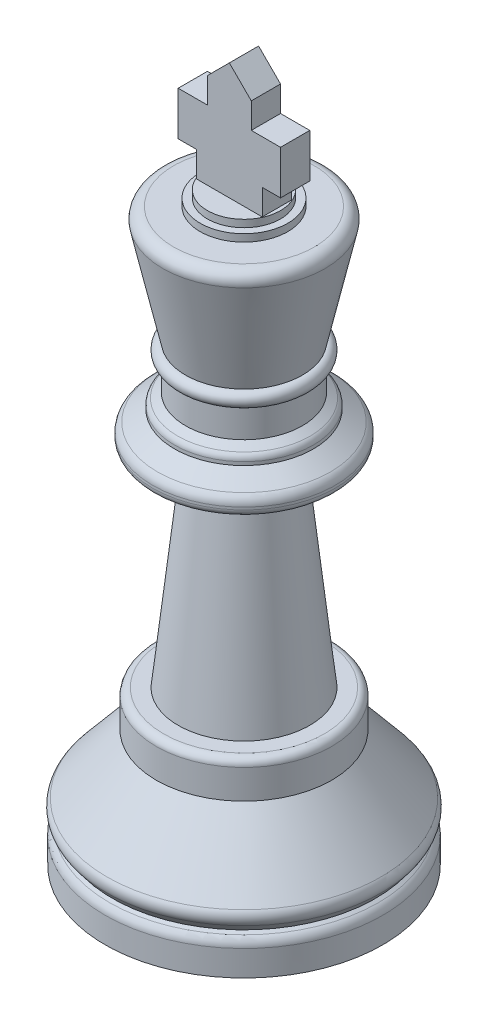
SolidWorks part; units mm, degrees
ref_plane "Front Plane" through (0, 0, 0) normal (0, 0, 1) x (1, 0, 0)
ref_plane "Top Plane" through (0, 0, 0) normal (0, 1, 0) x (1, 0, 0)
ref_plane "Right Plane" through (0, 0, 0) normal (1, 0, 0) x (0, 0, -1)
sketch "Sketch1" plane through (0, 0, 0) normal (0, 0, 1) x (1, 0, 0)
  line L0 (0, 0) -> (0, 80)
  line L1 (0, 80) -> (5, 80)
  line L2 (5, 80) -> (5, 79)
  line L3 (5, 79) -> (6, 79)
  line L4 (6, 79) -> (6, 78)
  line L5 (6, 78) -> (11.5, 78)
  line L6 (11.5, 78) -> (8, 62)
  line L8 (8, 60) -> (8, 56)
  line L9 (8, 56) -> (9.5, 55)
  line L10 (9.5, 55) -> (9.5, 54)
  line L11 (9.5, 54) -> (12.5, 52)
  line L12 (12.5, 52) -> (12.5, 50)
  line L13 (12.5, 50) -> (6, 49)
  line L14 (6, 49) -> (9, 21)
  line L15 (9, 21) -> (12, 21)
  line L16 (12, 21) -> (12, 16)
  line L17 (12, 16) -> (19.5, 7)
  line L18 (19.5, 7) -> (18, 5)
  line L19 (18, 5) -> (19, 4.25)
  line L20 (19, 4.25) -> (19, 0)
  line L21 (19, 0) -> (0, 0)
  arc A0 (8, 60) -> (8, 62) centre (8, 61) ccw
  dimension "D8" = 1
  dimension "D1" = 80
  dimension "D2" = 5
  dimension "D3" = 1
  dimension "D4" = 1
  dimension "D6" = 11.5
  dimension "D7" = 62
  dimension "D9" = 8
  dimension "D11" = 56
  dimension "D12" = 55
  dimension "D13" = 9.5
  dimension "D10" = 8
  dimension "D14" = 12.5
  dimension "D15" = 1
  dimension "D16" = 50
  dimension "D17" = 49
  dimension "D18" = 6
  dimension "D19" = 21
  dimension "D20" = 9
  dimension "D21" = 12
  dimension "D22" = 5
  dimension "D23" = 5
  dimension "18" = 18
  dimension "D25" = 19
  dimension "D26" = 7
  dimension "D24" = 19.5
revolve "Revolve1" add sketch "Sketch1" angle 360 about L0
sketch "Sketch2" plane through (0, 0, 0) normal (0, 0, 1) x (1, 0, 0)
  line L0 (0, 80) -> (0, 96)
  line L1 (5, 80) -> (-5, 80) construction
  line L2 (0, 96) -> (3, 93)
  line L3 (3, 93) -> (3, 89.5)
  line L4 (3, 89.5) -> (7, 89.5)
  line L5 (7, 89.5) -> (7, 83.5)
  line L6 (7, 83.5) -> (4.5, 83.5)
  line L7 (4.5, 83.5) -> (4.5, 80)
  line L8 (4.5, 80) -> (0, 80)
  dimension "D1" = 3.5
  dimension "D2" = 2.5
  dimension "D3" = 4.5
  dimension "D4" = 3
  dimension "D5" = 6
  dimension "D6" = 16
  dimension "D7" = 3.5
extrude "Boss-Extrude1" add sketch "Sketch2" along normal blind 2 and the other way blind 2
mirror "Mirror1" about plane through (0, 80, -2) normal (-1, 0, 0) of "Boss-Extrude1"
fillet "Fillet1" radius 1.5 4 edges at (0, 4.25, -19) (0, 7, -19.5) (0, 52, -12.5) (0, 78, -11.5)
fillet "Fillet2" radius 1 3 edges at (0, 55, -9.5) (0, 50, -12.5) (0, 21, -12)
equation "\"D6@Sketch1\"=23/2mm"
equation "\"D14@Sketch1\"=25/2"
equation "\"D13@Sketch1\"=19/2"
equation "\"D18@Sketch1\"=12/2"
equation "\"D20@Sketch1\"=18/2"
equation "\"D21@Sketch1\"=24/2"
equation "\"D25@Sketch1\"=38/2"
equation "\"D3@Sketch2\"=9/2"
